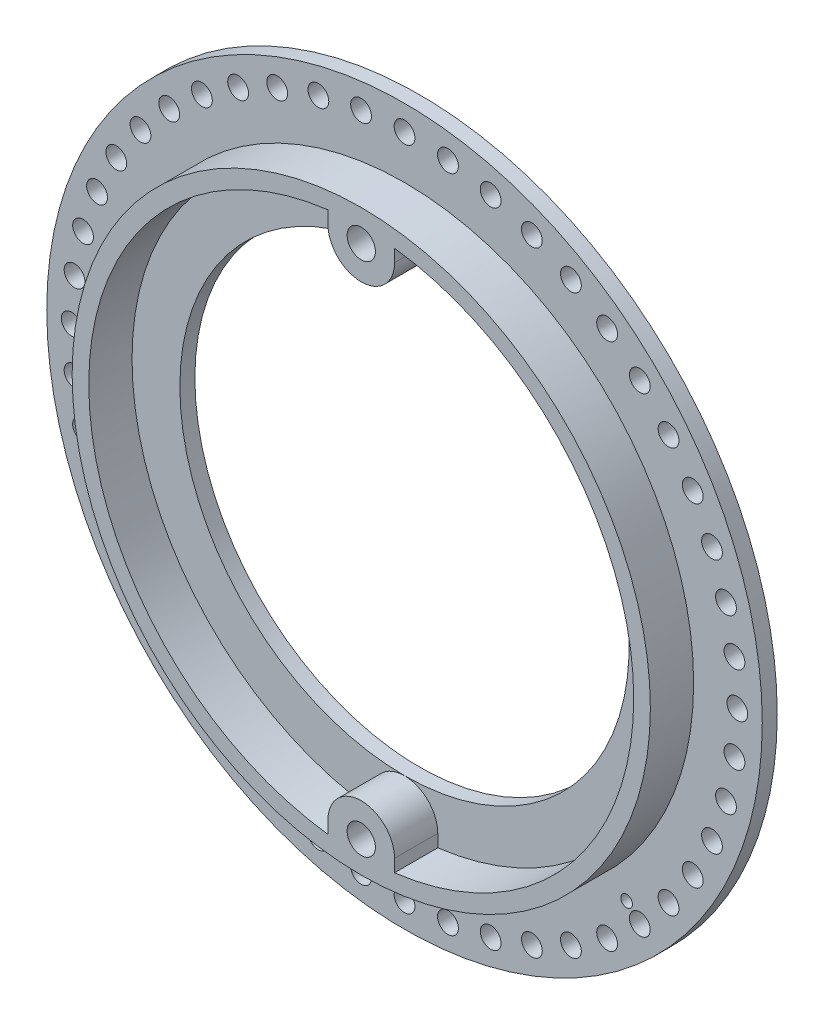
SolidWorks part; units mm, degrees
ref_plane "Front Plane" through (0, 0, 0) normal (0, 0, 1) x (1, 0, 0)
ref_plane "Top Plane" through (0, 0, 0) normal (0, 1, 0) x (1, 0, 0)
ref_plane "Right Plane" through (0, 0, 0) normal (1, 0, 0) x (0, 0, -1)
sketch "Sketch1" plane through (0, 0, 0) normal (0, 0, 1) x (1, 0, 0)
  circle A0 centre (0, 0) radius 43
  dimension "D1" = 86
extrude "Boss-Extrude1" add sketch "Sketch1" along normal blind 1.8
sketch "Sketch3" plane through (0, 0, 1.8) normal (0, 0, 1) x (1, 0, 0)
  line L0 (-4, 31) -> (-4, 32.5048)
  line L1 (4, 31) -> (4, 32.5048)
  line L2 (4, -31) -> (4, -32.5048)
  line L3 (-4, -31) -> (-4, -32.5048)
  circle A0 centre (0, 0) radius 34.75
  arc A1 (-4, 32.5048) -> (-4, -32.5048) centre (0, 0) ccw
  arc A2 (-4, 31) -> (4, 31) centre (0, 31) ccw
  circle A3 centre (0, 0) radius 32.75 construction
  arc A4 (4, -31) -> (-4, -31) centre (0, -31) ccw
  arc A5 (4, -32.5048) -> (4, 32.5048) centre (0, 0) ccw
  point P18 (0, 0)
  point P22 (-0.2453, 0)
  dimension "D1" = 69.5
  dimension "D3" = 8
  dimension "D5" = 2
  dimension "D4" = 31
  dimension "D2" = 2
extrude "Boss-Extrude2" add sketch "Sketch3" along normal blind 5.2 contours A1 L3 A4 L2 A5 L1 A2 L0 | A0
sketch "Sketch5" plane through (0, 0, 7) normal (0, 0, 1) x (1, 0, 0)
  circle A0 centre (0, -31) radius 1.7
  circle A1 centre (0, 31) radius 1.7
  point P7 (0, 0)
  dimension "D1" = 31
  dimension "D2" = 3.4
  dimension "D3" = 2
  dimension "D4" = 62
extrude "Cut-Extrude2" cut sketch "Sketch5" against normal up to surface (7 mm away) up to face at (43, 0, 0)
sketch "Sketch6" plane through (0, 0, 0) normal (0, 0, -1) x (-1, 0, 0)
  circle A0 centre (0, 31) radius 3
  circle A1 centre (0, -31) radius 3
  dimension "D1" = 6
  dimension "D2" = 6
  dimension "D3" = 31
  dimension "D4" = 31
extrude "Cut-Extrude3" cut sketch "Sketch6" against normal blind 4.5
sketch "Sketch7" plane through (0, 0, 0) normal (0, 0, -1) x (-1, 0, 0)
  circle A0 centre (0, 0) radius 27
  dimension "D1" = 54
extrude "Middle" cut sketch "Sketch7" against normal up to surface (1.8 mm away) up to face at (0, 0, 1.8)
sketch "Sketch8" plane through (0, 0, 1.8) normal (0, 0, 1) x (1, 0, 0)
  circle A0 centre (40, 0) radius 1.25
  circle A1 centre (39.6578, -5.221) radius 1.25
  circle A2 centre (38.637, -10.3528) radius 1.25
  circle A3 centre (36.9552, -15.3073) radius 1.25
  circle A4 centre (34.641, -20) radius 1.25
  circle A5 centre (31.7341, -24.3505) radius 1.25
  circle A6 centre (28.2843, -28.2843) radius 1.25
  circle A7 centre (24.3505, -31.7341) radius 1.25
  circle A8 centre (20, -34.641) radius 1.25
  circle A9 centre (15.3073, -36.9552) radius 1.25
  circle A10 centre (10.3528, -38.637) radius 1.25
  circle A11 centre (5.221, -39.6578) radius 1.25
  circle A12 centre (0, -40) radius 1.25
  circle A13 centre (-5.221, -39.6578) radius 1.25
  circle A14 centre (-10.3528, -38.637) radius 1.25
  circle A15 centre (-15.3073, -36.9552) radius 1.25
  circle A16 centre (-20, -34.641) radius 1.25
  circle A17 centre (-24.3505, -31.7341) radius 1.25
  circle A18 centre (-28.2843, -28.2843) radius 1.25
  circle A19 centre (-31.7341, -24.3505) radius 1.25
  circle A20 centre (-34.641, -20) radius 1.25
  circle A21 centre (-36.9552, -15.3073) radius 1.25
  circle A22 centre (-38.637, -10.3528) radius 1.25
  circle A23 centre (-39.6578, -5.221) radius 1.25
  circle A24 centre (-40, 0) radius 1.25
  circle A25 centre (-39.6578, 5.221) radius 1.25
  circle A26 centre (-38.637, 10.3528) radius 1.25
  circle A27 centre (-36.9552, 15.3073) radius 1.25
  circle A28 centre (-34.641, 20) radius 1.25
  circle A29 centre (-31.7341, 24.3505) radius 1.25
  circle A30 centre (-28.2843, 28.2843) radius 1.25
  circle A31 centre (-24.3505, 31.7341) radius 1.25
  circle A32 centre (-20, 34.641) radius 1.25
  circle A33 centre (-15.3073, 36.9552) radius 1.25
  circle A34 centre (-10.3528, 38.637) radius 1.25
  circle A35 centre (-5.221, 39.6578) radius 1.25
  circle A36 centre (0, 40) radius 1.25
  circle A37 centre (5.221, 39.6578) radius 1.25
  circle A38 centre (10.3528, 38.637) radius 1.25
  circle A39 centre (15.3073, 36.9552) radius 1.25
  circle A40 centre (20, 34.641) radius 1.25
  circle A41 centre (24.3505, 31.7341) radius 1.25
  circle A42 centre (28.2843, 28.2843) radius 1.25
  circle A43 centre (31.7341, 24.3505) radius 1.25
  circle A44 centre (34.641, 20) radius 1.25
  circle A45 centre (36.9552, 15.3073) radius 1.25
  circle A46 centre (38.637, 10.3528) radius 1.25
  circle A47 centre (39.6578, 5.221) radius 1.25
  point P104 (0, 0)
  dimension "D1" = 40
  dimension "D2" = 2.5
  dimension "D3" = 48
extrude "Cut-Extrude5" cut sketch "Sketch8" against normal up to surface (1.8 mm away) up to face at (-27, 0, 0)
fillet "Fillet1" radius 1.5 2 edges at (-3, -31, 4.5) (-3, 31, 4.5)
sketch "Alignment_Hole" plane through (0, 0, 0) normal (0, 0, -1) x (-1, 0, 0)
  line L0 (0, 0) -> (-49.8691, 0) construction
  line L1 (-5.6645, -5.6645) -> (-42.6819, -42.6819) construction
  circle A0 centre (-26.6933, -26.6933) radius 0.7
  circle A1 centre (-28.2843, -28.2843) radius 1.25 construction
  dimension "D1" = 1.4
  dimension "D2" = 2.25
  dimension "D3" = 45
extrude "Alignment_Hole - Cut" cut sketch "Alignment_Hole" against normal through all both and the other way through all
equation "\"D2@Sketch6\"=\"D1@Sketch6\""
